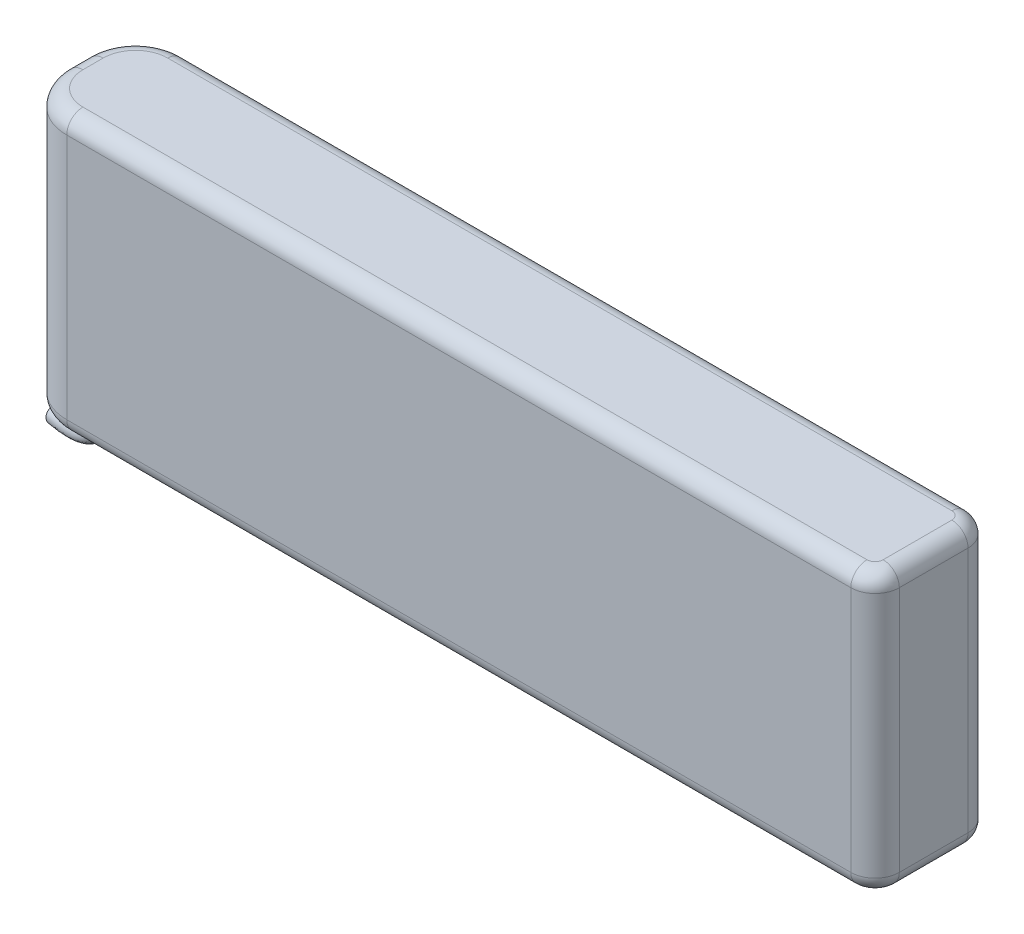
SolidWorks part; units mm, degrees
ref_plane "Front Plane" through (0, 0, 0) normal (0, 0, 1) x (1, 0, 0)
ref_plane "Top Plane" through (0, 0, 0) normal (0, 1, 0) x (1, 0, 0)
ref_plane "Right Plane" through (0, 0, 0) normal (1, 0, 0) x (0, 0, -1)
sketch "Sketch1" plane through (0, 0, 0) normal (0, 0, 1) x (1, 0, 0)
  line L1 (-53, -17.25) -> (53, -17.25)
  line L2 (-53, -17.25) -> (-53, 17.25)
  line L3 (-53, 17.25) -> (53, 17.25)
  line L4 (53, -17.25) -> (53, 17.25)
  line L5 (-53, -17.25) -> (53, 17.25) construction
  line L6 (-53, 17.25) -> (53, -17.25) construction
  point P0 (0, 0)
  dimension "D1" = 106
  dimension "D2" = 34.5
extrude "Boss-Extrude1" add sketch "Sketch1" along normal blind 14.5
fillet "Fillet1" radius 6 2 edges at (-53, 0, 14.5) (-53, 0, 0)
fillet "Fillet2" radius 3 2 edges at (53, 0, 14.5) (53, 0, 0)
fillet "Fillet3" radius 2 16 edges at (-51.2426, -17.25, 1.7574) (-53, -17.25, 7.25) (-51.2426, -17.25, 12.7426) (1.5, -17.25, 14.5) (52.1213, -17.25, 13.6213) (53, -17.25, 7.25) (52.1213, -17.25, 0.8787) (52.1213, 17.25, 0.8787) (53, 17.25, 7.25) (52.1213, 17.25, 13.6213) (1.5, 17.25, 14.5) (-51.2426, 17.25, 12.7426) (-53, 17.25, 7.25) (-51.2426, 17.25, 1.7574) (1.5, -17.25, 0) (1.5, 17.25, 0)
sketch "Sketch2" plane through (0, -17.25, 0) normal (0, -1, 0) x (-1, 0, 0)
  line L0 (47, -12.5) -> (47, -9.5) construction
  line L1 (51, -8.5) -> (51, -6) construction
  circle A0 centre (47, -9.5) radius 1
  circle A1 centre (47, -6.5) radius 1
  circle A2 centre (47, -9.5) radius 0.5
  circle A3 centre (47, -6.5) radius 0.5
  dimension "D1" = 2
  dimension "D2" = 2
  dimension "D5" = 1
  dimension "D6" = 1
  dimension "D3" = 3
  dimension "D4" = 4
sketch3d "3DSketch1"
  spline S1 degree 2 poles (-47, -17.25, 6.5) (-47.6393, -21.2613, 6.7454) (-53.2868, -20.6358, 6.1987) knots 0 0 0 1 1 1
  point P0 (-53.2868, -20.6358, 6.1987)
  point P5 (-35.555, -21.5937, 7.4042)
  point P8 (-35.8376, -22.9862, 6.9669)
  point P9 (-24.9544, -22.6327, -0.4335)
  point P11 (-35.7466, -18.0377, 8.6271)
  point P12 (-47.0207, -20.7706, 5.257)
  point P13 (-50.313, -13.4552, 9.521)
  point P14 (-51.3717, -14.3819, 11.4386)
  point P15 (-51.4249, -21.4454, 8.5012)
  point P16 (-46.8133, -20.9118, 6.3165)
sweep "Sweep1" add profiles "Sketch2" path "3DSketch1"
